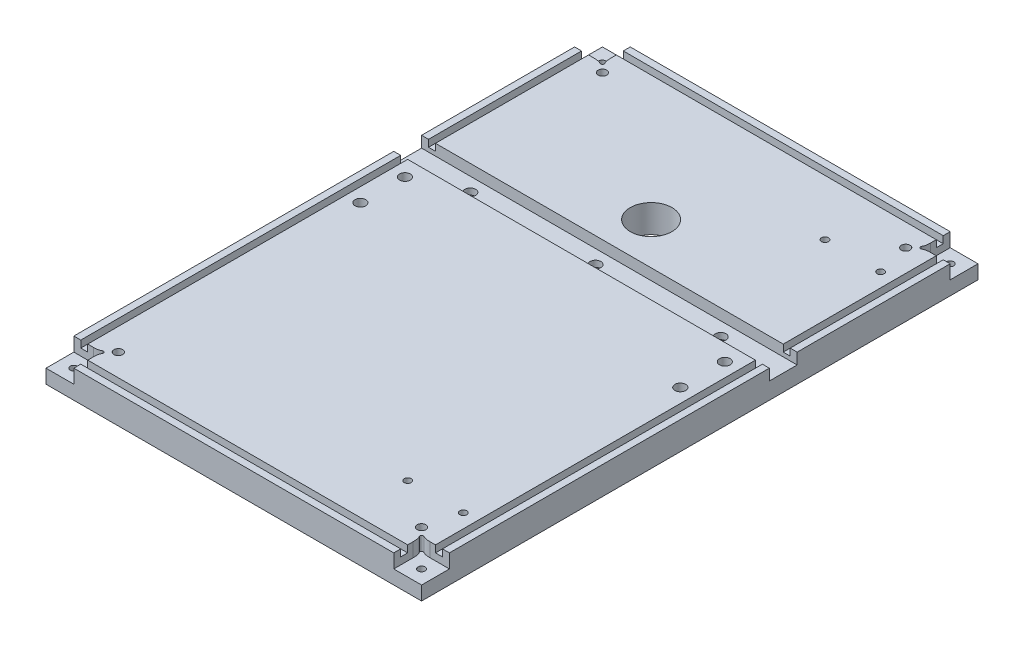
SolidWorks part; units mm, degrees
ref_plane "Front Plane" through (0, 0, 0) normal (0, 0, 1) x (1, 0, 0)
ref_plane "Top Plane" through (0, 0, 0) normal (0, 1, 0) x (1, 0, 0)
ref_plane "Right Plane" through (0, 0, 0) normal (1, 0, 0) x (0, 0, -1)
sketch "Base" plane through (0, 0, 0) normal (0, 1, 0) x (1, 0, 0)
  line L1 (-201.9764, 133.7508) -> (140.9236, 133.7508)
  line L2 (-201.9764, 133.7508) -> (-201.9764, -374.2492)
  line L3 (-201.9764, -374.2492) -> (140.9236, -374.2492)
  line L4 (140.9236, 133.7508) -> (140.9236, -374.2492)
  dimension "D1" = 342.9
  dimension "D2" = 508
extrude "Boss-Extrude1" add sketch "Base" along normal blind 25.4
sketch "Sketch2" plane through (0, 25.4, 0) normal (0, 1, 0) x (1, 0, 0)
  line L1 (172.6736, -31.3492) -> (-233.7264, -31.3492)
  line L2 (172.6736, -31.3492) -> (172.6736, -56.7492)
  line L3 (172.6736, -56.7492) -> (-233.7264, -56.7492)
  line L4 (-233.7264, -31.3492) -> (-233.7264, -56.7492)
  line L6 (140.9236, 133.7508) -> (-201.9764, 133.7508) construction
  line L9 (-30.5264, 133.7508) -> (-30.5264, -374.2492) construction
  line L10 (-201.9764, -374.2492) -> (140.9236, -374.2492) construction
  point P6 (-30.5264, -31.3492)
  dimension "D1" = 317.5
  dimension "D2" = 25.4
  dimension "D3" = 406.4
extrude "Cut-Extrude1" cut sketch "Sketch2" against normal blind 10.16
hole_wizard "CBORE for 3/8 Socket Head Cap Screw4" positions "3DSketch1" profile "Sketch3" counterbore size "3/8" standard "ANSI Inch" end condition up to next
sketch3d "3DSketch1"
  line L3 (-201.9764, 0, -133.7508) -> (-201.9764, 0, 374.2492) construction
  point P0 (83.7736, 0, 44.0492)
  point P2 (-30.5264, 0, 44.0492)
  point P4 (-144.8264, 0, 44.0492)
  dimension "D1" = 12.7
  dimension "D2" = 12.7
  dimension "D3" = 12.7
  dimension "D4" = 171.45
  dimension "D5" = 114.3
  dimension "D6" = 114.3
sketch "Sketch3" plane through (83.7736, 0, 44.0492) normal (1, 0, 0) x (0, 0, -1)
  line L0 (0, 0) -> (0, 15.24)
  line L1 (0, 15.24) -> (4.9022, 15.24)
  line L3 (4.9022, 15.24) -> (4.9022, 9.525)
  line L4 (4.9022, 9.525) -> (7.9375, 9.525)
  line L5 (7.9375, 9.525) -> (7.9375, 0)
  line L7 (7.9375, 0) -> (0, 0)
  line L11 (0, -6.35) -> (0, 107.95) construction
  dimension "Thru Hole Dia." = 9.8044
  dimension "Thru Hole Depth" = 15.24
  dimension "C'Bore Dia." = 15.875
  dimension "C'Bore Depth" = 9.525
hole_wizard "CBORE for 3/8 Socket Head Cap Screw3" positions "Sketch4" profile "Sketch6" counterbore size "3/8" standard "ANSI Inch" end condition up to next
sketch "Sketch4" plane through (0, 0, 0) normal (0, -1, 0) x (-1, 0, 0)
  line L0 (201.9764, -56.7492) -> (-140.9236, -56.7492) construction
  line L1 (-140.9236, -374.2492) -> (-140.9236, 133.7508) construction
  line L3 (201.9764, 133.7508) -> (201.9764, -374.2492) construction
  point P0 (-115.5236, -71.9892)
  point P2 (-115.5236, -112.6292)
  point P4 (176.5764, -71.9892)
  point P6 (176.5764, -112.6292)
  dimension "D1" = 15.24
  dimension "D2" = 25.4
  dimension "D3" = 25.4
  dimension "D4" = 40.64
  dimension "D5" = 15.24
  dimension "D6" = 25.4
  dimension "D7" = 40.64
  dimension "D8" = 25.4
sketch "Sketch6" plane through (115.5236, 0, 71.9892) normal (1, 0, 0) x (0, 0, -1)
  line L0 (0, 0) -> (0, 25.4)
  line L1 (0, 25.4) -> (4.9022, 25.4)
  line L3 (4.9022, 25.4) -> (4.9022, 15.24)
  line L4 (4.9022, 15.24) -> (7.9375, 15.24)
  line L5 (7.9375, 15.24) -> (7.9375, 0)
  line L7 (7.9375, 0) -> (0, 0)
  line L11 (0, -6.35) -> (0, 107.95) construction
  dimension "Thru Hole Dia." = 9.8044
  dimension "Thru Hole Depth" = 25.4
  dimension "C'Bore Dia." = 15.875
  dimension "C'Bore Depth" = 15.24
hole_wizard "CBORE for 1/4 Socket Head Cap Screw1" positions "3DSketch2" profile "Sketch9" counterbore size "1/4" standard "ANSI Inch" end condition up to next
sketch3d "3DSketch2"
  line L0 (140.9236, 0, -133.7508) -> (-201.9764, 0, -133.7508) construction
  line L1 (140.9236, 0, 374.2492) -> (140.9236, 0, -133.7508) construction
  line L2 (-201.9764, 0, -133.7508) -> (-201.9764, 0, 374.2492) construction
  line L3 (-201.9764, 0, 374.2492) -> (140.9236, 0, 374.2492) construction
  point P0 (128.2236, 0, 361.5492)
  point P2 (-189.2764, 0, 361.5492)
  point P4 (-189.2764, 0, -121.0508)
  point P6 (128.2236, 0, -121.0508)
  dimension "D1" = 12.7
  dimension "D2" = 12.7
  dimension "D3" = 12.7
  dimension "D4" = 12.7
  dimension "D5" = 12.7
  dimension "D6" = 12.7
  dimension "D7" = 12.7
  dimension "D8" = 12.7
sketch "Sketch9" plane through (128.2236, 0, 361.5492) normal (1, 0, 0) x (0, 0, -1)
  line L0 (0, 0) -> (0, 25.4)
  line L1 (0, 25.4) -> (3.2639, 25.4)
  line L3 (3.2639, 25.4) -> (3.2639, 6.35)
  line L4 (3.2639, 6.35) -> (5.5562, 6.35)
  line L5 (5.5562, 6.35) -> (5.5562, 0)
  line L7 (5.5562, 0) -> (0, 0)
  line L11 (0, -6.35) -> (0, 107.95) construction
  dimension "Thru Hole Dia." = 6.5278
  dimension "Thru Hole Depth" = 25.4
  dimension "C'Bore Dia." = 11.1125
  dimension "C'Bore Depth" = 6.35
sketch "Sketch8" plane through (0, 25.4, 0) normal (0, 1, 0) x (1, 0, 0)
  line L0 (116.3173, -347.4744) -> (115.5236, -348.8492) construction
  line L1 (140.9236, -374.2492) -> (115.5236, -374.2492)
  line L2 (140.9236, -374.2492) -> (140.9236, -348.8492)
  line L3 (140.9236, -348.8492) -> (123.1436, -348.8492)
  line L4 (115.5236, -374.2492) -> (115.5236, -356.4692)
  line L5 (-201.9764, -374.2492) -> (-176.5764, -374.2492)
  line L6 (-201.9764, -374.2492) -> (-201.9764, -348.8492)
  line L7 (-201.9764, -348.8492) -> (-184.1964, -348.8492)
  line L8 (-176.5764, -374.2492) -> (-176.5764, -356.4692)
  line L9 (-201.9764, 133.7508) -> (-176.5764, 133.7508)
  line L10 (-201.9764, 133.7508) -> (-201.9764, 108.3508)
  line L11 (-201.9764, 108.3508) -> (-184.1964, 108.3508)
  line L12 (-176.5764, 133.7508) -> (-176.5764, 115.9708)
  line L13 (140.9236, 133.7508) -> (115.5236, 133.7508)
  line L14 (140.9236, 133.7508) -> (140.9236, 108.3508)
  line L15 (140.9236, 108.3508) -> (123.1436, 108.3508)
  line L16 (115.5236, 133.7508) -> (115.5236, 115.9708)
  line L17 (115.5236, -348.8492) -> (123.1436, -348.8492) construction
  line L18 (115.5236, -356.4692) -> (115.5236, -348.8492) construction
  line L19 (115.5236, -348.8492) -> (114.1488, -349.6429) construction
  line L20 (115.5236, 108.3508) -> (116.3173, 106.976) construction
  line L21 (115.5236, 108.3508) -> (114.1488, 109.1446) construction
  line L22 (-176.5764, 108.3508) -> (-175.2016, 109.1446) construction
  line L23 (-176.5764, 108.3508) -> (-177.3702, 106.976) construction
  line L24 (-176.5764, -348.8492) -> (-175.2016, -349.6429) construction
  line L25 (-176.5764, -348.8492) -> (-177.3702, -347.4744) construction
  arc A0 (116.3173, -347.4744) -> (114.1488, -349.6429) centre (115.5236, -348.8492) ccw
  arc A1 (114.1488, 109.1446) -> (116.3173, 106.976) centre (115.5236, 108.3508) ccw
  arc A2 (-177.3702, 106.976) -> (-175.2016, 109.1446) centre (-176.5764, 108.3508) ccw
  arc A3 (-175.2016, -349.6429) -> (-177.3702, -347.4744) centre (-176.5764, -348.8492) ccw
  spline S0 degree 3 poles (123.1436, -348.8492) (120.8225, -348.8492) (118.3275, -348.6349) (116.3173, -347.4744) knots 0 0 0 0 1 1 1 1
  spline S1 degree 3 poles (115.5236, -356.4692) (115.5236, -353.9168) (115.3093, -351.6531) (114.1488, -349.6429) knots 0 0 0 0 1 1 1 1
  spline S2 degree 3 poles (123.1436, 108.3508) (120.8225, 108.3508) (118.3275, 108.1366) (116.3173, 106.976) knots 0 0 0 0 1 1 1 1
  spline S3 degree 3 poles (114.1488, 109.1446) (115.3093, 111.1547) (115.5236, 113.6497) (115.5236, 115.9708) knots 0 0 0 0 1 1 1 1
  spline S4 degree 3 poles (-176.5764, 115.9708) (-176.5764, 113.4184) (-176.3621, 111.1547) (-175.2016, 109.1446) knots 0 0 0 0 1 1 1 1
  spline S5 degree 3 poles (-177.3702, 106.976) (-179.3803, 108.1366) (-181.8753, 108.3508) (-184.1964, 108.3508) knots 0 0 0 0 1 1 1 1
  spline S6 degree 3 poles (-175.2016, -349.6429) (-176.7942, -352.4013) (-176.5764, -354.9687) (-176.5764, -356.4692) knots 0 0 0 0 1 1 1 1
  spline S7 degree 3 poles (-177.3702, -347.4744) (-180.1285, -349.0669) (-182.696, -348.8492) (-184.1964, -348.8492) knots 0 0 0 0 1 1 1 1
  point P23 (117.1111, -348.8492)
  point P27 (115.5236, -350.4367)
  dimension "D9" = 7.62
  dimension "D10" = 1.5875
  dimension "D15" = 60
  dimension "D16" = 1.5875
  dimension "D20" = 3.175
  dimension "D25" = 60
  dimension "D28" = 3.175
  dimension "D2" = 25.4
  dimension "D3" = 25.4
  dimension "D4" = 25.4
  dimension "D5" = 25.4
  dimension "D6" = 25.4
  dimension "D7" = 25.4
  dimension "D8" = 25.4
  dimension "D11" = 7.62
  dimension "D12" = 25.4
  dimension "D13" = 60
  dimension "D14" = 60
  dimension "D17" = 60
  dimension "D18" = 7.62
  dimension "D19" = 7.62
  dimension "D21" = 60
  dimension "D22" = 60
  dimension "D23" = 7.62
  dimension "D24" = 7.62
  dimension "D26" = 60
  dimension "D27" = 7.62
  dimension "D29" = 7.62
extrude "Cut-Extrude3" cut sketch "Sketch8" against normal blind 12.7
sketch "Sketch10" plane through (0, 25.4, 0) normal (0, 1, 0) x (1, 0, 0)
  line L1 (128.2236, 108.3508) -> (134.5736, 108.3508)
  line L2 (128.2236, 108.3508) -> (128.2236, -348.8492)
  line L3 (128.2236, -348.8492) -> (134.5736, -348.8492)
  line L4 (134.5736, 108.3508) -> (134.5736, -348.8492)
  line L5 (140.9236, -348.8492) -> (140.9236, -56.7492) construction
  line L8 (-201.9764, 108.3508) -> (-201.9764, -31.3492) construction
  line L9 (-195.6264, 108.3508) -> (-189.2764, 108.3508)
  line L10 (-195.6264, 108.3508) -> (-195.6264, -348.8492)
  line L11 (-195.6264, -348.8492) -> (-189.2764, -348.8492)
  line L12 (-189.2764, 108.3508) -> (-189.2764, -348.8492)
  line L13 (-184.1964, -348.8492) -> (-201.9764, -348.8492) construction
  line L14 (-201.9764, 108.3508) -> (-184.1964, 108.3508) construction
  line L15 (123.1436, 108.3508) -> (140.9236, 108.3508) construction
  line L16 (140.9236, -348.8492) -> (123.1436, -348.8492) construction
  line L17 (-176.5764, 115.9708) -> (-176.5764, 133.7508) construction
  line L18 (-176.5764, 127.4008) -> (115.5236, 127.4008)
  line L19 (-176.5764, 127.4008) -> (-176.5764, 121.0508)
  line L20 (-176.5764, 121.0508) -> (115.5236, 121.0508)
  line L21 (115.5236, 127.4008) -> (115.5236, 121.0508)
  line L22 (115.5236, 133.7508) -> (115.5236, 115.9708) construction
  line L23 (115.5236, 133.7508) -> (-176.5764, 133.7508) construction
  line L24 (-176.5764, -374.2492) -> (-176.5764, -356.4692) construction
  line L25 (-176.5764, -361.5492) -> (115.5236, -361.5492)
  line L26 (-176.5764, -361.5492) -> (-176.5764, -367.8992)
  line L27 (-176.5764, -367.8992) -> (115.5236, -367.8992)
  line L28 (115.5236, -361.5492) -> (115.5236, -367.8992)
  line L29 (115.5236, -356.4692) -> (115.5236, -374.2492) construction
  line L30 (-176.5764, -374.2492) -> (115.5236, -374.2492) construction
  dimension "D1" = 6.35
  dimension "D2" = 6.35
  dimension "D3" = 6.35
  dimension "D4" = 6.35
  dimension "D5" = 6.35
  dimension "D6" = 6.35
  dimension "D7" = 6.35
  dimension "D8" = 6.35
extrude "Cut-Extrude4" cut sketch "Sketch10" against normal blind 6.35
hole_wizard "3/8-16 Tapped Hole2" positions "Sketch17" profile "Sketch18" tap size "3/8-16" standard "ANSI Inch" end condition up to next
sketch "Sketch17" plane through (0, 0, 0) normal (0, -1, 0) x (-1, 0, 0)
  line L0 (-140.9236, 133.7508) -> (201.9764, 133.7508) construction
  line L1 (-140.9236, -374.2492) -> (-140.9236, 133.7508) construction
  line L2 (201.9764, 133.7508) -> (201.9764, -374.2492) construction
  line L3 (201.9764, -374.2492) -> (-140.9236, -374.2492) construction
  point P0 (-107.9036, -341.2292)
  point P2 (168.9564, -341.2292)
  point P4 (168.9564, 100.7308)
  point P6 (-107.9036, 100.7308)
  dimension "D1" = 33.02
  dimension "D2" = 33.02
  dimension "D3" = 33.02
  dimension "D4" = 33.02
  dimension "D5" = 33.02
  dimension "D6" = 33.02
  dimension "D7" = 33.02
  dimension "D8" = 33.02
sketch "Sketch18" plane through (107.9036, 0, 341.2292) normal (1, 0, 0) x (0, 0, -1)
  line L0 (0, 0) -> (0, 25.4)
  line L1 (0, 25.4) -> (3.9687, 25.4)
  line L2 (3.9687, 25.4) -> (3.9687, 0)
  line L5 (3.9687, 0) -> (0, 0)
  line L11 (0, -6.35) -> (0, 107.95) construction
  dimension "Thru Tap Drill Dia." = 7.9375
  dimension "Thru Tap Drill Depth" = 25.4
cosmetic thread "Hole Thread5" parameters "D2"=9.525
cosmetic thread "Hole Thread6" parameters "D2"=9.525
cosmetic thread "Hole Thread7" parameters "D2"=9.525
cosmetic thread "Hole Thread8" parameters "D2"=9.525
sketch "Sketch19" plane through (0, 0, 0) normal (0, -1, 0) x (1, 0, 0)
  circle A0 centre (-168.9564, -100.7308) radius 9.525
  circle A1 centre (-168.9564, 341.2292) radius 9.525
  circle A2 centre (107.9036, 341.2292) radius 9.525
  circle A3 centre (108.2173, -100.7308) radius 9.525
  dimension "D1" = 19.05
  dimension "D2" = 19.05
  dimension "D3" = 19.05
  dimension "D4" = 19.05
extrude "Cut-Extrude5" cut sketch "Sketch19" against normal blind 1.27
ref_plane "Plane1" through (0, 0, 120.2492) normal (0, 0, 1) x (1, 0, 0)
sketch "Sketch20" plane through (0, 0, 0) normal (0, -1, 0) x (1, 0, 0)
  line L0 (-30.5264, -133.7508) -> (-30.5264, 374.2492) construction
  line L1 (140.9236, -133.7508) -> (-201.9764, -133.7508) construction
  line L2 (-201.9764, 374.2492) -> (140.9236, 374.2492) construction
  line L3 (128.2236, 31.3492) -> (-189.2764, 31.3492) construction
  circle A0 centre (115.5236, 310.7492) radius 3.175 construction
  circle A1 centre (64.7236, 310.7492) radius 3.175 construction
  circle A2 centre (115.5236, 310.7492) radius 3.175
  circle A3 centre (64.7236, 310.7492) radius 3.175
  circle A4 centre (64.7236, -70.2508) radius 3.175 construction
  circle A5 centre (115.5236, -70.2508) radius 3.175 construction
  circle A6 centre (64.7236, -70.2508) radius 3.175
  circle A7 centre (115.5236, -70.2508) radius 3.175
  circle A8 centre (-30.5264, -6.7508) radius 19.05
  dimension "D1" = 38.1
  dimension "D2" = 38.1
extrude "Cut-Extrude6" cut sketch "Sketch20" against normal through all
